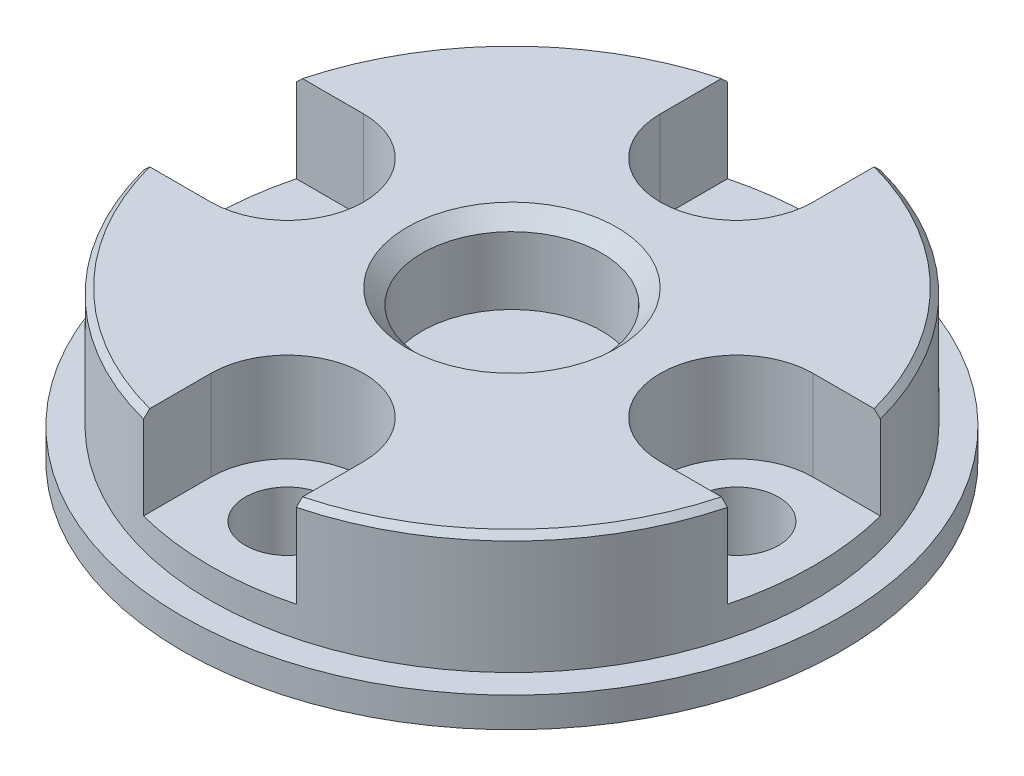
SolidWorks part; units mm, degrees
ref_plane "Front Plane" through (0, 0, 0) normal (0, 0, 1) x (1, 0, 0)
ref_plane "Top Plane" through (0, 0, 0) normal (0, 1, 0) x (1, 0, 0)
ref_plane "Right Plane" through (0, 0, 0) normal (1, 0, 0) x (0, 0, -1)
sketch "Sketch1" plane through (0, 0, 0) normal (0, 1, 0) x (1, 0, 0)
  circle A0 centre (0, 0) radius 11
  dimension "D1" = 22
extrude "Boss-Extrude1" add sketch "Sketch1" along normal blind 1
sketch "Sketch2" plane through (0, 1, 0) normal (0, 1, 0) x (1, 0, 0)
  circle A0 centre (0, 0) radius 10.075
  dimension "D1" = 20.15
extrude "Boss-Extrude2" add sketch "Sketch2" along normal blind 4
chamfer "Chamfer1" distance 0.2 angle 45 1 edges at (0, 5, 10.075)
sketch "Sketch3" plane through (0, 5, 0) normal (0, 1, 0) x (1, 0, 0)
  circle A0 centre (0, 7.5) radius 1.4
  circle A1 centre (7.5, 0) radius 1.4
  circle A2 centre (0, -7.5) radius 1.4
  circle A3 centre (-7.5, 0) radius 1.4
  point P2 (0, 0)
  point P12 (0, 0)
  dimension "D1" = 2.8
  dimension "D2" = 7.5
extrude "Cut-Extrude1" cut sketch "Sketch3" against normal through all
sketch "Sketch4" plane through (0, 5, 0) normal (0, 1, 0) x (1, 0, 0)
  line L0 (-2.55, 7.5) -> (-2.55, 9.747)
  line L1 (2.55, 7.5) -> (2.55, 9.747)
  line L2 (7.5, -2.55) -> (9.747, -2.55)
  line L3 (7.5, 2.55) -> (9.747, 2.55)
  line L4 (-2.55, -7.5) -> (-2.55, -9.747)
  line L5 (2.55, -7.5) -> (2.55, -9.747)
  line L6 (-7.5, 2.55) -> (-9.747, 2.55)
  line L7 (-7.5, -2.55) -> (-9.747, -2.55)
  arc A0 (-2.55, 7.5) -> (2.55, 7.5) centre (0, 7.5) ccw
  circle A1 centre (0, 0) radius 10.075 construction
  circle A2 centre (0, 0) radius 10.075 construction
  arc A3 (-2.55, 9.747) -> (2.55, 9.747) centre (0, 0) cw
  arc A4 (7.5, 2.55) -> (7.5, -2.55) centre (7.5, 0) ccw
  arc A5 (9.747, 2.55) -> (9.747, -2.55) centre (0, 0) cw
  arc A6 (2.55, -7.5) -> (-2.55, -7.5) centre (0, -7.5) ccw
  arc A7 (2.55, -9.747) -> (-2.55, -9.747) centre (0, 0) cw
  arc A8 (-7.5, -2.55) -> (-7.5, 2.55) centre (-7.5, 0) ccw
  arc A9 (-9.747, -2.55) -> (-9.747, 2.55) centre (0, 0) cw
  point P29 (0, 0)
  dimension "D1" = 5.1
extrude "Cut-Extrude2" cut sketch "Sketch4" against normal offset from surface (3 mm away) 2 up to face at (0, 0, -6.1)
sketch "Sketch5" plane through (0, 5, 0) normal (0, 1, 0) x (1, 0, 0)
  circle A0 centre (0, 0) radius 3
  dimension "D1" = 6
extrude "Cut-Extrude3" cut sketch "Sketch5" against normal blind 2.75
chamfer "Chamfer2" distance 0.5 angle 45 1 edges at (0, 5, 3)
